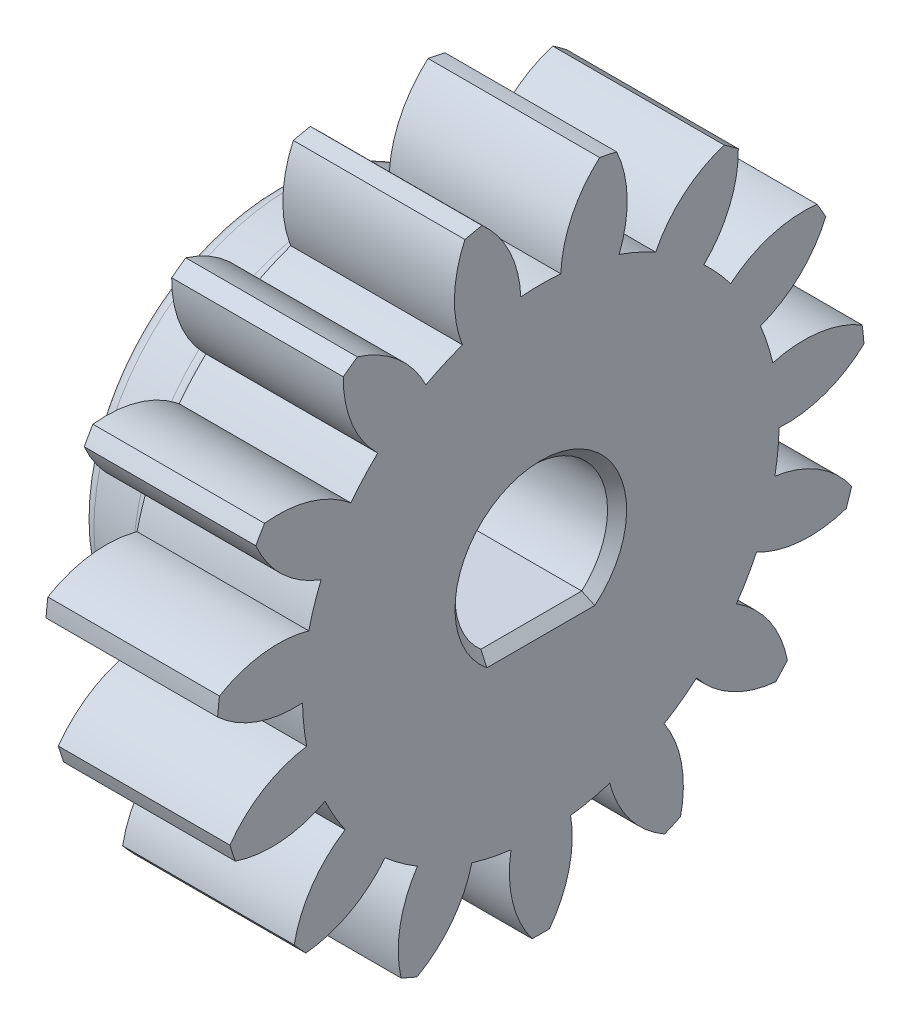
SolidWorks part; units mm, degrees
ref_plane "Plane1" through (0, 0, 0) normal (0, 0, 1) x (1, 0, 0)
ref_plane "Plane2" through (0, 0, 0) normal (0, 1, 0) x (1, 0, 0)
ref_plane "Plane3" through (0, 0, 0) normal (1, 0, 0) x (0, 0, -1)
sketch "HoldingSke" plane through (0, 0, 0) normal (0, 1, 0) x (1, 0, 0)
  line L0 (0, 0) -> (0.483, -0.1294)
  line L1 (-15, 0) -> (100, 0) construction
  line L2 (0, 0) -> (-2.1039, 2.3779)
  line L3 (0, 0) -> (-11.863, 4.5341)
  line L4 (0, 0) -> (8.3417, 2.2352)
  line L5 (0, 0) -> (-13.1173, -4.8924)
  line L6 (0, 0) -> (-7.4607, -5.0337)
  line L7 (-2.1039, 2.3779) -> (0.9096, 16.0498)
  line L8 (-76.2, 54.61) -> (-74.8, 54.61)
  line L9 (-71.009, 38.7566) -> (-53.1078, 45.2721)
  line L10 (-76.2, 71.12) -> (104.1128, 71.12)
  line L11 (0, 0) -> (-9, 0)
  line L12 (-76.2, 101.6) -> (-76.133, 101.6)
  line L13 (24.9733, 27.94) -> (52.9518, 28.4284)
  line L14 (24.9733, 27.94) -> (24.9743, 27.94)
  line L15 (24.9733, 27.94) -> (100.4006, 29.5858)
  line L16 (-63.627, -2) -> (-12.827, -2)
  circle A0 centre (0, 0) radius 4
  circle A1 centre (0, 0) radius 11
  circle A2 centre (0, 0) radius 11
  circle A3 centre (0, 0) radius 4
  dimension "Num_teeth" = 15
  dimension "Pitch_radius" = 180.3128
  dimension "Width" = 9
  dimension "Thickness" = 9
sketch "BasProSke" plane through (0, 0, 0) normal (0, 1, 0) x (1, 0, 0)
  line L0 (-10, 0) -> (60, 0) construction
  line L1 (0, 0) -> (0, 17)
  line L2 (0, 0) -> (9, 0)
  line L3 (9, 0) -> (9, 17)
  line L4 (9, 17) -> (0, 17)
  dimension "Thickness" = 9
  dimension "Diameter" = 34
revolve "Base-Revolve" add sketch "BasProSke" angle 360 about L0
sketch "TooCutSke" plane through (0, 0, 0) normal (1, 0, 0) x (0, 0, -1)
  line L1 (0, 0) -> (0, 107) construction
  line L2 (0, 0) -> (-1.6851, 14.905) construction
  line L3 (0, 0) -> (-6.2081, 29.2069) construction
  line L4 (-1.6851, 14.905) -> (-3.1041, 14.6034) construction
  arc A0 (1.0501, 12.4548) -> (-1.0501, 12.4548) centre (0, 0) ccw
  arc A1 (3.1109, 16.7388) -> (-3.1109, 16.7388) centre (0, 0) ccw
  circle A2 centre (0, 0) radius 15 construction
  circle A3 centre (0, 0) radius 14.0954 construction
  arc A4 (-1.0501, 12.4548) -> (-3.1109, 16.7388) centre (-7.045, 12.2085) ccw
  arc A5 (3.1109, 16.7388) -> (1.0501, 12.4548) centre (7.045, 12.2085) ccw
extrude "ToothCut" cut sketch "TooCutSke" along normal through all
fillet "Breaks" [suppressed] radius 0.04 tangent propagation no
fillet "RootFillets" [suppressed] radius 0.501
pattern_circular "TeethCuts" count 15 every 24 about axis through (-10, 0, 0) along (1, 0, 0) of "ToothCut", "RootFillets", "Breaks"
sketch "HubNeaOneSke" plane through (0, 0, 0) normal (-1, 0, 0) x (0, 0, 1)
  circle A0 centre (0, 0) radius 11
  dimension "Diameter" = 22
extrude "HubNearOne" add sketch "HubNeaOneSke" along normal blind 5.0001
sketch "HubNeaBotSke" plane through (0, 0, 0) normal (-1, 0, 0) x (0, 0, 1)
  circle A0 centre (0, 0) radius 11
  dimension "Diameter" = 22
extrude "HubNearBoth" [suppressed] add sketch "HubNeaBotSke" along normal blind 2.5
ref_plane "FarPln" through (9, 0, 0) normal (1, 0, 0) x (0, 0, -1)
sketch "HubFarSke" plane through (9, 0, 0) normal (1, 0, 0) x (0, 0, -1)
  circle A0 centre (0, 0) radius 11
  dimension "Diameter" = 22
extrude "HubFar" [suppressed] add sketch "HubFarSke" along normal blind 2.5
sketch "BorSke" plane through (0, 0, 0) normal (1, 0, 0) x (0, 0, -1)
  circle A0 centre (0, 0) radius 4
  dimension "Diameter" = 8
extrude "Bore" cut sketch "BorSke" along normal mid plane 28.0001
sketch "KeySke" plane through (0, 0, 0) normal (1, 0, 0) x (0, 0, -1)
  line L0 (-1.5, 0) -> (-1.5, 5.4)
  line L1 (-1.5, 5.4) -> (1.5, 5.4)
  line L2 (1.5, 5.4) -> (1.5, 0)
  line L3 (0, 0) -> (0, 34) construction
  line L4 (-1.5, 0) -> (1.5, 0)
  dimension "Width" = 3
extrude "Keyway" [suppressed] cut sketch "KeySke" along normal mid plane 28.0001
pattern_circular "Keyway2" [suppressed] count 2 every 90 about axis through (-10, 0, 0) along (1, 0, 0) reverse direction yes
sketch "Szkic1" plane through (0, 0, 0) normal (1, 0, 0) x (0, 0, -1)
  line L0 (-4.7612, 4) -> (4.8559, 4) construction
  line L1 (-2.6458, -3) -> (2.6458, -3)
  line L2 (-2.6458, -3) -> (-2.6458, -4)
  line L3 (-2.6458, -4) -> (2.6458, -4)
  line L4 (2.6458, -3) -> (2.6458, -4)
  circle A0 centre (0, 0) radius 4 construction
  dimension "D1" = 7
extrude "Dodanie-wyciągnięcie1" add sketch "Szkic1" along normal through all and the other way through all
draft "Pochylenie1" type of draft neutral plane draft angle 10 faces to draft 1 face at (-5.0001, 0, 11) neutral plane through (0, 0, 0) neutral plane normal (-1, 0, 0) parameters "D1"=10
fillet "Zaokrąglenie1" radius 2 1 edges at (0, 0, -11)
fillet "Zaokrąglenie2" radius 1 1 edges at (-5.0001, 0, 10.1184)
chamfer "Sfazowanie1" distance 0.5 angle 45 4 edges at (-5.0001, 4, 0) (-5.0001, -3, 0) (9, -3, 0) (9, 4, 0)
equation "' \"Module@HoldingSke\" = 6.35"
equation "' \"Num_teeth@HoldingSke\" = 12"
equation "' \"Ap@HoldingSke\" =  20"
equation "' \"Ap@HoldingSke\" = 20"
equation "' \"Width@HoldingSke\" = 0.5 * 25.4"
equation "' \"Hub_dia@HoldingSke\"= 1 * 25.4"
equation "' \"Hub_dia@HoldingSke\" = 1 * 25.4"
equation "' \"Overall_len@HoldingSke\" = 1.0 * 25.4"
equation "' \"Bore@HoldingSke\" = 0.75 * 25.4"
equation "' \"T_dim@HoldingSke\" = 0.1 * 25.4"
equation "' \"Width@KeySke\" = 0.25 * 25.4"
equation "' \"Show_teeth@HoldingSke\" = 13"
equation "' \"Backlash@HoldingSke\" = 0.009 * 25.4"
equation "' \"Addendum_fac@HoldingSke\" = 1.0"
equation "' \"Dedendum_fac@HoldingSke\" = 1.25"
equation "' \"Dedendum_add@HoldingSke\" = 0.00005 * 25.4"
equation "' \"Clearance_fac@HoldingSke\" = 0.25"
equation "\"Pitch@HoldingSke\" = 1 / \"Module@HoldingSke\""
equation "\"Overcut_dia@TooCutSke\" = (\"Num_teeth@HoldingSke\" + 2 * \"Addendum_fac@HoldingSke\") / \"Pitch@HoldingSke\" + 0.002 * 25.4"
equation "\"Pitch_dia@TooCutSke\" = \"Num_teeth@HoldingSke\" / \"Pitch@HoldingSke\""
equation "\"Base_dia@TooCutSke\" = \"Num_teeth@HoldingSke\" / \"Pitch@HoldingSke\" * cos((\"Ap@HoldingSke\"  * 3.14159265 / 180))"
equation "\"Root_dia@TooCutSke\" = (\"Num_teeth@HoldingSke\" + 2) / \"Pitch@HoldingSke\" - 2 * (\"Addendum_fac@HoldingSke\" + \"Dedendum_fac@HoldingSke\") / \"Pitch@HoldingSke\" - \"Dedendum_add@HoldingSke\" * 2"
equation "\"Half_ang@TooCutSke\" = 180 / \"Num_teeth@HoldingSke\""
equation "\"Half_CT@TooCutSke\" = \"Num_teeth@HoldingSke\" / \"Pitch@HoldingSke\" * sin((3.14159265 / 2 / \"Num_teeth@HoldingSke\")) / 2 - 7 * \"Backlash@HoldingSke\" / 4"
equation "\"Flank_rad@TooCutSke\" = \"Num_teeth@HoldingSke\" / \"Pitch@HoldingSke\" / 5"
equation "\"Radius@RootFillets\" = \"Clearance_fac@HoldingSke\" / \"Pitch@HoldingSke\" + \"Dedendum_add@HoldingSke\""
equation "\"Break_rad@Breaks\" = 0.02 / \"Pitch@HoldingSke\""
equation "\"Thickness@HoldingSke\" = \"Width@HoldingSke\""
equation "\"OAL@HoldingSke\" = \"Thickness@HoldingSke\""
equation "\"MHD@HoldingSke\" = (\"Num_teeth@HoldingSke\" + 2) / \"Pitch@HoldingSke\" - 2 * (\"Addendum_fac@HoldingSke\" + \"Dedendum_fac@HoldingSke\")  / \"Pitch@HoldingSke\" - \"Dedendum_add@HoldingSke\" * 2"
equation "\"MBD@HoldingSke\" = (\"Num_teeth@HoldingSke\" + 2) / \"Pitch@HoldingSke\" - 2 * (\"Addendum_fac@HoldingSke\" + \"Dedendum_fac@HoldingSke\")  / \"Pitch@HoldingSke\" - \"Dedendum_add@HoldingSke\" * 2 - 0.002 * 25.4"
equation "\"MHD@HoldingSke\" = ((sgn( \"MHD@HoldingSke\" - \"Hub_dia@HoldingSke\" )-1)*( \"MHD@HoldingSke\" - \"Hub_dia@HoldingSke\" ))/-2+ \"Hub_dia@HoldingSke\""
equation "\"MBD@HoldingSke\" = ((sgn( \"MBD@HoldingSke\" - \"Bore@HoldingSke\" )-1)*( \"MBD@HoldingSke\" - \"Bore@HoldingSke\" ))/-2+ \"Bore@HoldingSke\""
equation "\"OAL@HoldingSke\" = ((sgn( \"OAL@HoldingSke\" - \"Overall_len@HoldingSke\" )+1)*( \"OAL@HoldingSke\" - \"Overall_len@HoldingSke\" ))/2 + \"Overall_len@HoldingSke\" + 0.000002 * 25.4"
equation "\"Num_teeth@TeethCuts\" = int( \"Show_teeth@HoldingSke\" ) + 1"
equation "\"Num_teeth@TeethCuts\" = ((sgn( \"Num_teeth@TeethCuts\" - \"Num_teeth@HoldingSke\" )-1)*( \"Num_teeth@TeethCuts\" - \"Num_teeth@HoldingSke\" ))/-2+ \"Num_teeth@HoldingSke\""
equation "\"Num_teeth@TeethCuts\" = ((sgn( \"Num_teeth@TeethCuts\" - 2.0)+1)*( \"Num_teeth@TeethCuts\" - 2.0))/2 +2.0"
equation "\"Angle@TeethCuts\" = 360.0 / \"Num_teeth@HoldingSke\""
equation "\"Diameter@BasProSke\" = (\"Num_teeth@HoldingSke\" + 2 * \"Addendum_fac@HoldingSke\") / \"Pitch@HoldingSke\""
equation "\"Thickness@BasProSke\"  = \"Thickness@HoldingSke\""
equation "' \"Fillet_rad@BasProSke\" =  \"Thickness@HoldingSke\" * 0.05"
equation "' \"Fillet_rad@BasProSke\" = \"Thickness@HoldingSke\" * 0.05"
equation "\"MHD@HoldingSke\" = ((sgn( \"MHD@HoldingSke\" - \"Root_dia@TooCutSke\" )-1)*( \"MHD@HoldingSke\" - \"Root_dia@TooCutSke\" ))/-2+ \"Root_dia@TooCutSke\""
equation "\"Diameter@HubNeaOneSke\" = \"MHD@HoldingSke\""
equation "\"Length@HubNearOne\" = \"OAL@HoldingSke\" - \"Thickness@BasProSke\""
equation "\"Diameter@HubNeaBotSke\" = \"MHD@HoldingSke\""
equation "\"Length@HubNearBoth\" = ( \"OAL@HoldingSke\" - \"Thickness@BasProSke\" ) / 2.0"
equation "\"Thickness@FarPln\" = \"Thickness@BasProSke\""
equation "\"Diameter@HubFarSke\" = \"MHD@HoldingSke\""
equation "\"Length@HubFar\" = ( \"OAL@HoldingSke\" - \"Thickness@BasProSke\" ) / 2.0"
equation "\"Diameter@BorSke\" = \"MBD@HoldingSke\""
equation "\"D1@Bore\" = \"OAL@HoldingSke\" * 2.0"
equation "\"D1@Keyway\" = \"OAL@HoldingSke\" * 2.0"
equation "\"Offset@KeySke\" = \"T_dim@HoldingSke\" + \"MBD@HoldingSke\" / 2.0"
